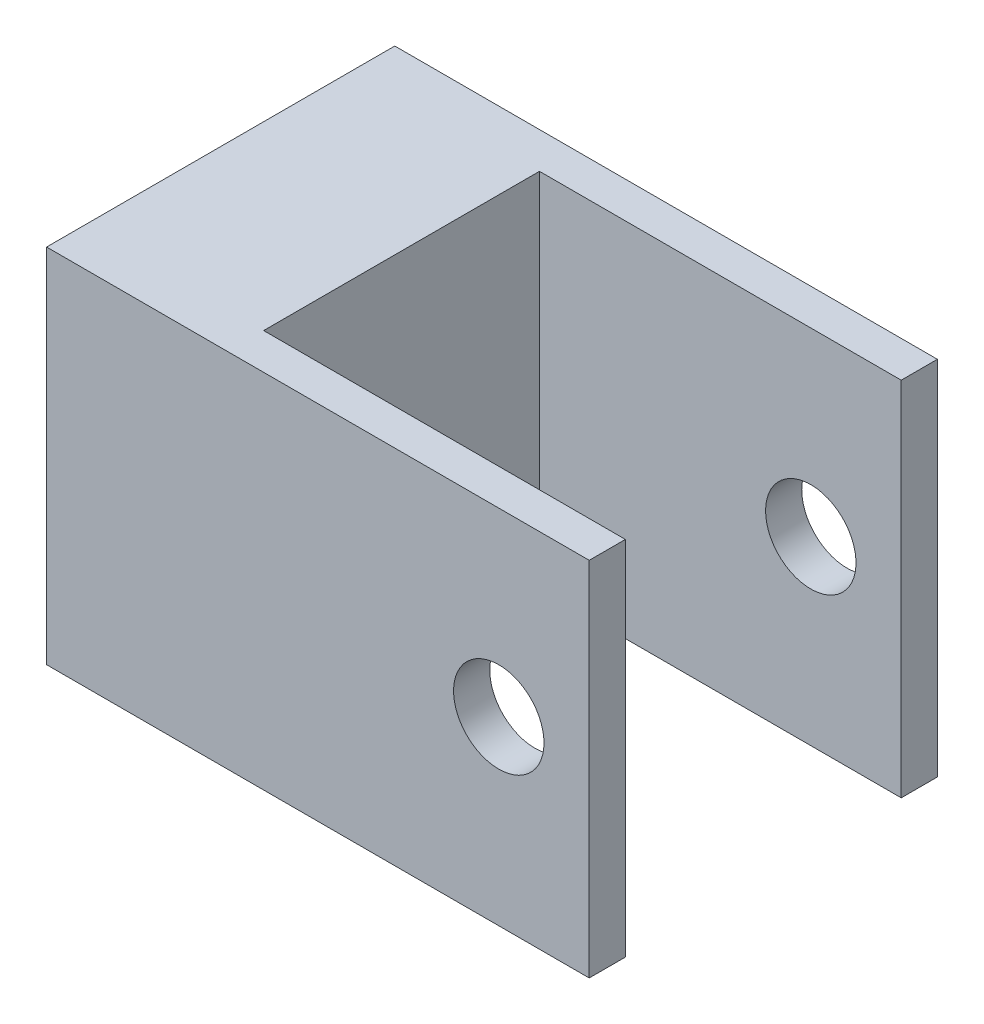
SolidWorks part; units mm, degrees
ref_plane "前视基准面" through (0, 0, 0) normal (0, 0, 1) x (1, 0, 0)
ref_plane "上视基准面" through (0, 0, 0) normal (0, 1, 0) x (1, 0, 0)
ref_plane "右视基准面" through (0, 0, 0) normal (1, 0, 0) x (0, 0, -1)
other "Configuration Table"
sketch "Sketch1" plane through (0, 0, 0) normal (0, 1, 0) x (1, 0, 0)
  line L1 (0, -38.5) -> (120, -38.5)
  line L2 (0, -38.5) -> (0, 38.5)
  line L3 (0, 38.5) -> (120, 38.5)
  line L4 (120, -38.5) -> (120, 38.5)
  line L5 (0, -38.5) -> (120, 38.5) construction
  line L6 (0, 38.5) -> (120, -38.5) construction
  point P0 (60, 0)
extrude "Boss-Extrude1" add sketch "Sketch1" along normal blind 40 and the other way blind 40
sketch "Sketch2" plane through (0, 0, 0) normal (0, 1, 0) x (1, 0, 0)
  line L0 (120, -38.5) -> (120, 38.5) construction
  line L1 (40, -30.5) -> (120, -30.5)
  line L2 (40, -30.5) -> (40, 30.5)
  line L3 (40, 30.5) -> (120, 30.5)
  line L4 (120, -30.5) -> (120, 30.5)
  line L5 (40, -30.5) -> (120, 30.5) construction
  line L6 (40, 30.5) -> (120, -30.5) construction
  point P0 (80, 0)
extrude "Cut-Extrude1" cut sketch "Sketch2" along normal blind 100 and the other way blind 100
sketch "Sketch3" plane through (0, 0, 0) normal (0, 0, 1) x (1, 0, 0)
  circle A0 centre (100, 0) radius 10
extrude "Cut-Extrude2" cut sketch "Sketch3" along normal blind 100 and the other way blind 100
ref_plane "mid_plane_y" through (0, 0, 0) normal (0, 1, 0) x (1, 0, 0)
ref_plane "base_face" through (0, 0, 0) normal (1, 0, 0) x (0, 0, -1)
sketch3d "3DSketch1"
  line L0 (100, -38.5, 0) -> (100, 38.5, 0) construction
ref_axis "hinge_axis_y" through (100, -38.5, 0) along (0, 1, 0)
